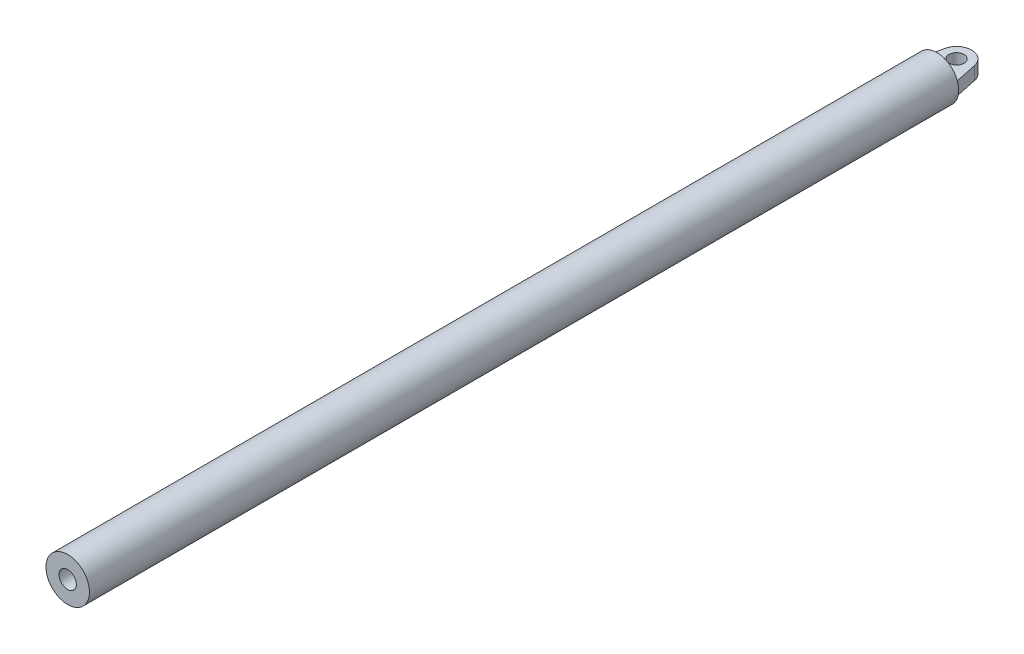
SolidWorks part; units mm, degrees
ref_plane "Front Plane" through (0, 0, 0) normal (0, 0, 1) x (1, 0, 0)
ref_plane "Top Plane" through (0, 0, 0) normal (0, 1, 0) x (1, 0, 0)
ref_plane "Right Plane" through (0, 0, 0) normal (1, 0, 0) x (0, 0, -1)
sketch "Sketch1" plane through (0, 0, 0) normal (0, 0, 1) x (1, 0, 0)
  circle A0 centre (0, 0) radius 50
  dimension "D1" = 100
extrude "Boss-Extrude1" add sketch "Sketch1" along normal blind 2000
sketch "Sketch2" plane through (0, 0, 0) normal (0, 1, 0) x (1, 0, 0)
  line L0 (-45, 0) -> (-34.2808, 52.0586)
  line L1 (50, 0) -> (-50, 0) construction
  line L2 (34.2808, 52.0586) -> (45, 0)
  line L3 (-45, 0) -> (45, 0)
  circle A0 centre (0, 45) radius 17.5
  arc A1 (-34.2808, 52.0586) -> (34.2808, 52.0586) centre (0, 45) cw
  dimension "D1" = 35
  dimension "D2" = 35
  dimension "D3" = 45
  dimension "D4" = 45
  dimension "D5" = 45
extrude "Boss-Extrude2" add sketch "Sketch2" along normal mid plane 30
shell "Shell1" thickness 30 removed face at (50, 0, 2000)
